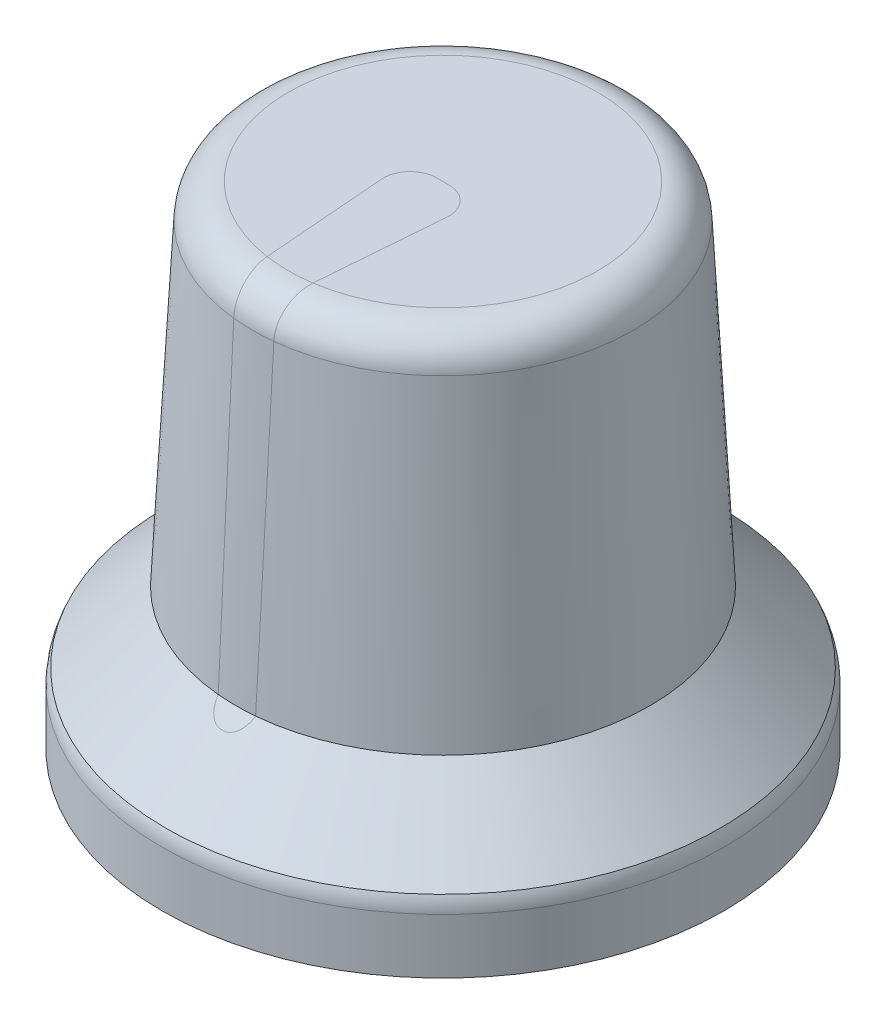
SolidWorks part; units mm, degrees
ref_plane "Front Plane" through (0, 0, 0) normal (0, 0, 1) x (1, 0, 0)
ref_plane "Top Plane" through (0, 0, 0) normal (0, 1, 0) x (1, 0, 0)
ref_plane "Right Plane" through (0, 0, 0) normal (1, 0, 0) x (0, 0, -1)
sketch "Sketch1" plane through (0, 0, 0) normal (0, 1, 0) x (1, 0, 0)
  circle A0 centre (0, 0) radius 8
  dimension "D1" = 16
extrude "Boss-Extrude1" add sketch "Sketch1" along normal blind 2
sketch "Sketch2" plane through (0, 2, 0) normal (0, 1, 0) x (1, 0, 0)
  circle A0 centre (0, 0) radius 6
  circle A1 centre (0, 0) radius 8
  circle A2 centre (0, 0) radius 8 construction
  dimension "D2" = 12
  dimension "D1" = 0
extrude "Boss-Extrude2" add sketch "Sketch2" along normal blind 12 draft 3
fillet "Fillet1" radius 1.016 1 edges at (0, 14, 5.3711)
chamfer "Chamfer1" distance 1.905 angle 45 1 edges at (0, 2, 6) first distance on face at (0, 2, 8)
fillet "Fillet3" radius 1.016 1 edges at (0, 2, 8)
sketch "Sketch3" plane through (0, 14, 0) normal (0, 1, 0) x (1, 0, 0)
  line L0 (0, -6.2915) -> (0, 0) construction
  line L1 (0.175, 0) -> (-0.175, 0)
  line L2 (0.9346, -0.8224) -> (0.5372, -5.8238)
  line L3 (0.0308, -6.2915) -> (-0.0308, -6.2915)
  line L4 (-0.9346, -0.8224) -> (-0.5372, -5.8238)
  circle A0 centre (0, 0) radius 5.8946 construction
  circle A1 centre (0, 0) radius 4.407
  circle A2 centre (0, 0) radius 4.407 construction
  circle A3 centre (0, 0) radius 5.8946 construction
  arc A4 (-0.175, 0) -> (-0.9346, -0.8224) centre (-0.175, -0.762) ccw
  arc A5 (0.175, 0) -> (0.9346, -0.8224) centre (0.175, -0.762) cw
  arc A6 (-0.0308, -6.2915) -> (-0.5372, -5.8238) centre (-0.0308, -5.7835) cw
  arc A7 (0.5372, -5.8238) -> (0.0308, -6.2915) centre (0.0308, -5.7835) cw
  point P7 (0, 0)
  point P10 (0, -6.2915)
  point P14 (-1, 0)
  point P17 (1, 0)
  point P20 (-0.5, -6.2915)
  point P23 (0.5, -6.2915)
  dimension "D2" = 6.2915
  dimension "D5" = 0.762
  dimension "D6" = 0.508
  dimension "D3" = 2
  dimension "D4" = 1
  dimension "D1" = 0
split line "Split Line2"
sketch "Sketch4" plane through (0, 14, 0) normal (0, 1, 0) x (1, 0, 0)
  line L3 (-0.9346, -0.8224) -> (-0.6536, -4.3582)
  line L4 (0.6536, -4.3582) -> (0.9346, -0.8224)
  line L5 (0.175, 0) -> (-0.175, 0)
  line L6 (-0.9346, -0.8224) -> (-0.6536, -4.3582)
  line L7 (0.6536, -4.3582) -> (0.9346, -0.8224)
  line L8 (0.175, 0) -> (-0.175, 0)
  arc A3 (-0.6536, -4.3582) -> (0.6536, -4.3582) centre (0, 0) ccw
  arc A4 (0.9346, -0.8224) -> (0.175, 0) centre (0.175, -0.762) ccw
  arc A5 (-0.175, 0) -> (-0.9346, -0.8224) centre (-0.175, -0.762) ccw
  arc A6 (-0.6536, -4.3582) -> (0.6536, -4.3582) centre (0, 0) ccw
  arc A7 (0.9346, -0.8224) -> (0.175, 0) centre (0.175, -0.762) ccw
  arc A8 (-0.175, 0) -> (-0.9346, -0.8224) centre (-0.175, -0.762) ccw
  dimension "D1" = 0
